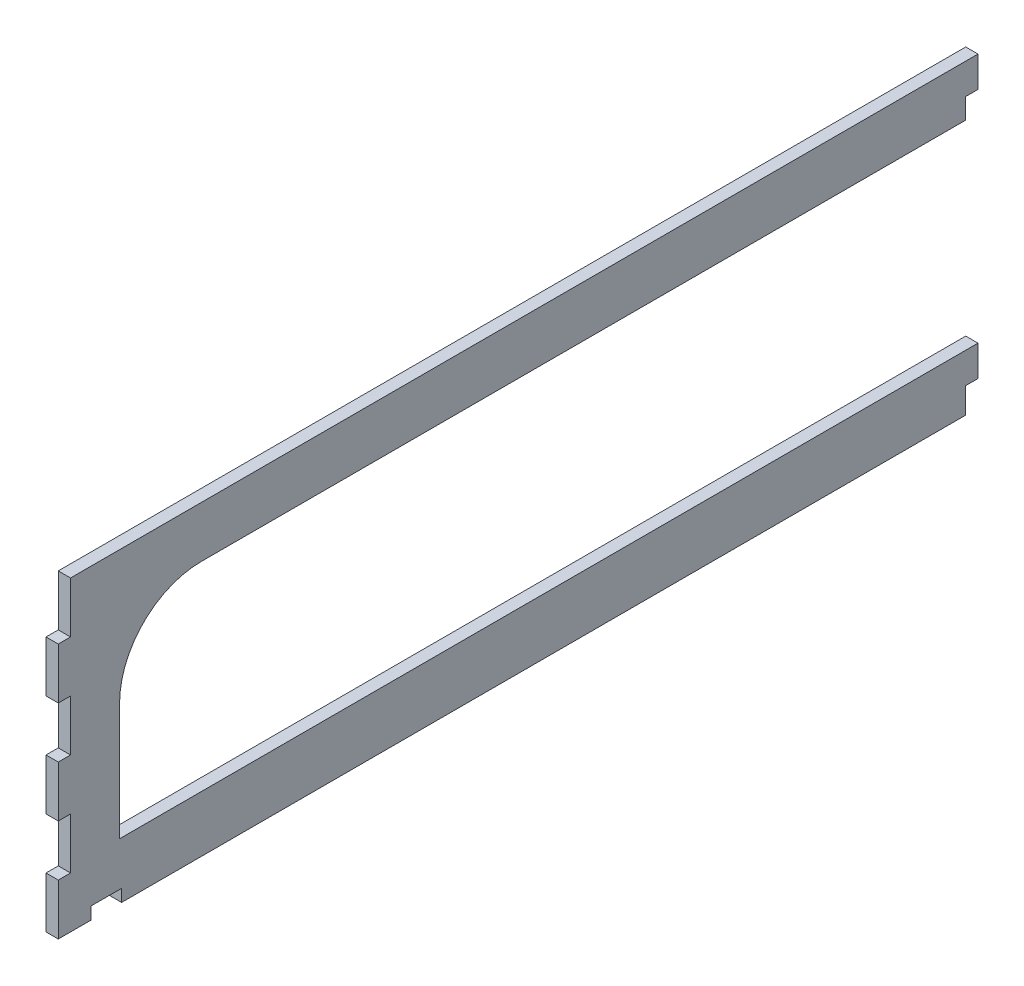
SolidWorks part; units mm, degrees
ref_plane "Front" through (0, 0, 0) normal (0, 0, 1) x (1, 0, 0)
ref_plane "Top" through (0, 0, 0) normal (0, 1, 0) x (1, 0, 0)
ref_plane "Right" through (0, 0, 0) normal (1, 0, 0) x (0, 0, -1)
sketch "Sketch1" plane through (0, 0, 0) normal (1, 0, 0) x (0, 0, -1)
  line L0 (450, 125) -> (450, 150)
  line L1 (0, 0) -> (450, 0)
  line L2 (0, 0) -> (0, 150)
  line L3 (0, 150) -> (450, 150)
  line L4 (450, 0) -> (450, 27.5)
  line L5 (450, 125) -> (30, 125)
  line L7 (450, 27.5) -> (30, 27.5)
  line L8 (30, 125) -> (30, 27.5)
  dimension "D1" = 420
  dimension "D2" = 150
  dimension "D3" = 27.5
  dimension "D4" = 25
  dimension "D5" = 30
extrude "Boss-Extrude1" add sketch "Sketch1" along normal blind 6
sketch "Sketch2" plane through (6, 0, 0) normal (1, 0, 0) x (0, 0, -1)
  line L1 (0, 150) -> (6, 150)
  line L2 (0, 150) -> (0, 125)
  line L3 (0, 125) -> (6, 125)
  line L4 (6, 150) -> (6, 125)
  dimension "D1" = 6
  dimension "D2" = 25
extrude "Cut-Extrude1" cut sketch "Sketch2" against normal blind 6
pattern_linear "LPattern1" count 3 spacing 50 along (0, -1, 0) of "Cut-Extrude1"
fillet "Fillet1" radius 40 1 edges at (3, 125, -30)
sketch "Sketch3" plane through (0, 0, 0) normal (-1, 0, 0) x (0, 0, 1)
  line L0 (-450, 0) -> (-450, 27.5) construction
  line L1 (-450, 135) -> (-444, 135)
  line L2 (-450, 135) -> (-450, 125)
  line L3 (-450, 125) -> (-444, 125)
  line L4 (-444, 135) -> (-444, 125)
  line L5 (-70, 125) -> (-450, 125) construction
  line L7 (-450, 12.5) -> (-444, 12.5)
  line L8 (-450, 12.5) -> (-450, 0)
  line L9 (-450, 0) -> (-444, 0)
  line L10 (-444, 12.5) -> (-444, 0)
  line L11 (0, 0) -> (-450, 0) construction
  line L12 (-450, 125) -> (-450, 150) construction
  point P4 (-450, 10.7307)
  point P13 (-450, 135)
  dimension "D1" = 6
  dimension "D2" = 10
  dimension "D3" = 12.5
extrude "Cut-Extrude2" cut sketch "Sketch3" against normal through all
sketch "Sketch4" plane through (0, 0, 0) normal (-1, 0, 0) x (0, 0, 1)
  line L0 (0, 0) -> (-444, 0) construction
  line L1 (-16, 0) -> (-31, 0)
  line L2 (-16, 0) -> (-16, 6)
  line L3 (-16, 6) -> (-31, 6)
  line L4 (-31, 0) -> (-31, 6)
  line L5 (-6, 25) -> (-6, 50) construction
  dimension "D1" = 10
  dimension "D2" = 15
  dimension "D3" = 6
extrude "Cut-Extrude3" cut sketch "Sketch4" against normal through all
